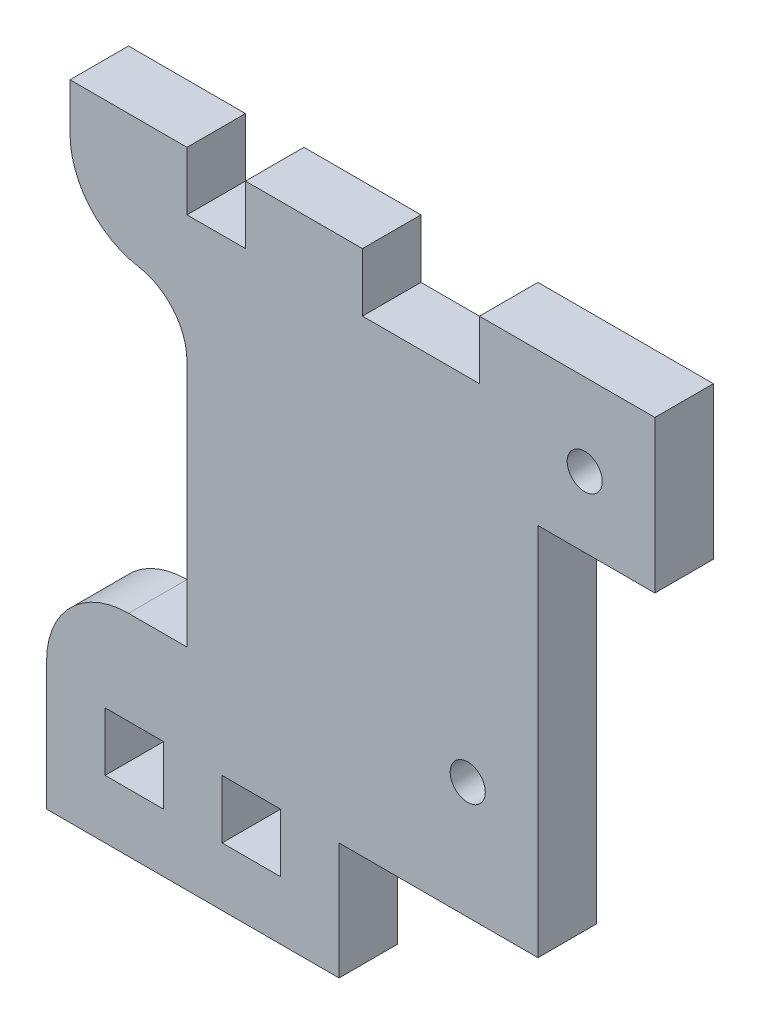
SolidWorks part; units mm, degrees
ref_plane "Plan de face" through (0, 0, 0) normal (0, 0, 1) x (1, 0, 0)
ref_plane "Plan de dessus" through (0, 0, 0) normal (0, 1, 0) x (1, 0, 0)
ref_plane "Plan de droite" through (0, 0, 0) normal (1, 0, 0) x (0, 0, -1)
sketch "Esquisse1" plane through (0, 0, 0) normal (0, 0, 1) x (1, 0, 0)
  line L0 (25, 0) -> (42, 0)
  line L1 (5, 0) -> (10, 0)
  line L2 (0, 0) -> (0, 8)
  line L3 (12, 40) -> (17, 40)
  line L4 (52, 32) -> (52, 45)
  line L5 (27, 40) -> (37, 40)
  line L6 (2, 40) -> (2, 45)
  line L7 (2, 45) -> (12, 45)
  line L8 (12, 40) -> (12, 45)
  line L9 (15, 0) -> (20, 0)
  line L10 (17, 40) -> (17, 45)
  line L11 (17, 45) -> (27, 45)
  line L12 (27, 40) -> (27, 45)
  line L13 (15, 0) -> (15, -5)
  line L14 (10, -5) -> (5, -5)
  line L15 (10, 0) -> (10, -5)
  line L16 (5, 0) -> (5, -5)
  line L18 (0, 0) -> (0, -5.81)
  line L19 (2, 34) -> (2, 40)
  line L20 (0, 8) -> (12, 8)
  line L22 (2, 34) -> (12, 34)
  line L23 (12, 8) -> (12, 34)
  line L24 (20, 0) -> (20, -5)
  line L25 (42, 0) -> (42, 32)
  line L26 (42, 32) -> (52, 32)
  line L27 (37, 40) -> (37, 45)
  line L28 (37, 45) -> (52, 45)
  line L30 (25, 0) -> (25, -4.929)
  line L31 (20, -5) -> (15, -5)
  line L32 (25, -4.929) -> (25, -10)
  line L33 (25, -10) -> (0, -10)
  line L34 (0, -5.81) -> (0, -10)
  circle A0 centre (46, 38) radius 1.5
  circle A1 centre (36, 10) radius 1.5
  dimension "D9" = 3
  dimension "D11" = 28
  dimension "D2" = 6
  dimension "D3" = 10
  dimension "D4" = 5
  dimension "D5" = 5
  dimension "D6" = 10
  dimension "D7" = 8
  dimension "D8" = 26
  dimension "D10" = 5
  dimension "D12" = 10
  dimension "D13" = 10
  dimension "D14" = 10
  dimension "D15" = 6
  dimension "D16" = 7
  dimension "D17" = 15
  dimension "D18" = 40
  dimension "D19" = 2
  dimension "D20" = 5
  dimension "D21" = 5
  dimension "D22" = 5
  dimension "D23" = 5
  dimension "D24" = 25
  dimension "D25" = 17
extrude "Boss.-Extru.1" add sketch "Esquisse1" along normal blind 5
fillet "Congé1" radius 7 2 edges at (0, 8, 2.5) (2, 34, 2.5)
fillet "Congé2" radius 5 1 edges at (12, 34, 2.5)
